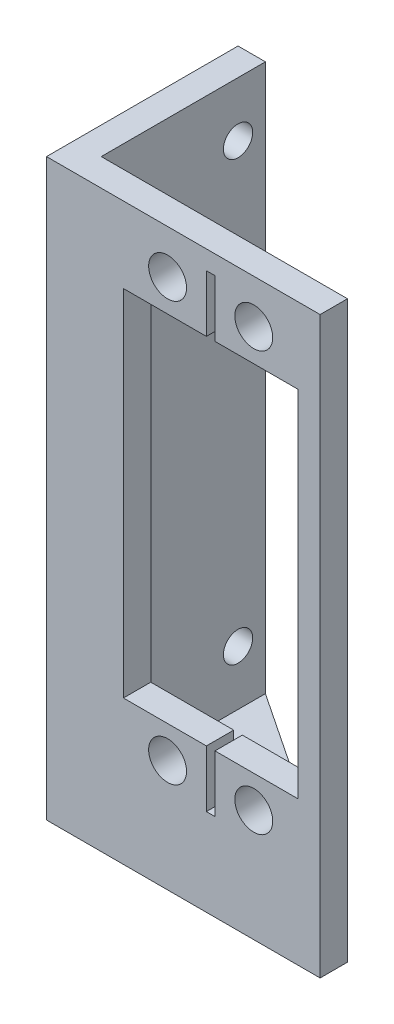
SolidWorks part; units mm, degrees
ref_plane "Front Plane" through (0, 0, 0) normal (0, 0, 1) x (1, 0, 0)
ref_plane "Top Plane" through (0, 0, 0) normal (0, 1, 0) x (1, 0, 0)
ref_plane "Right Plane" through (0, 0, 0) normal (1, 0, 0) x (0, 0, -1)
sketch "Sketch2" plane through (0, 0, 0) normal (0, 0, 1) x (1, 0, 0)
  line L1 (0, 0) -> (31.75, 0)
  line L2 (0, 0) -> (0, 63.5)
  line L3 (0, 63.5) -> (31.75, 63.5)
  line L4 (31.75, 0) -> (31.75, 63.5)
  dimension "D1" = 63.5
  dimension "D2" = 31.75
extrude "Boss-Extrude1" add sketch "Sketch2" along normal blind 3.175 contours L4 L3 L2 L1
sketch "Sketch3" plane through (0, 0, 3.175) normal (0, 0, 1) x (1, 0, 0)
  line L0 (8.923, 54.704) -> (29.177, 13.55) construction
  line L1 (8.923, 54.704) -> (18.55, 54.704)
  line L2 (8.923, 54.704) -> (8.923, 13.55)
  line L3 (8.923, 13.55) -> (18.55, 13.55)
  line L4 (29.177, 54.704) -> (29.177, 13.55)
  line L5 (29.177, 54.704) -> (8.923, 13.55) construction
  line L6 (14.05, 58.427) -> (24.05, 9.827) construction
  line L7 (14.05, 9.827) -> (24.05, 58.427) construction
  line L8 (19.55, 13.55) -> (29.177, 13.55)
  line L9 (18.55, 13.55) -> (18.55, 6.946)
  line L10 (18.55, 6.946) -> (19.55, 6.946)
  line L11 (19.55, 13.55) -> (19.55, 6.946)
  line L12 (19.05, 34.127) -> (62.1329, 34.127) construction
  line L13 (18.55, 61.308) -> (19.55, 61.308)
  line L14 (18.55, 54.704) -> (18.55, 61.308)
  line L15 (19.55, 54.704) -> (19.55, 61.308)
  line L16 (19.55, 54.704) -> (29.177, 54.704)
  line L17 (0, 0) -> (0, 63.5) construction
  line L18 (0, 63.5) -> (31.75, 63.5) construction
  circle A0 centre (14.05, 9.827) radius 2.2
  circle A1 centre (24.05, 9.827) radius 2.2
  circle A2 centre (14.05, 58.427) radius 2.2
  circle A3 centre (24.05, 58.427) radius 2.2
  point P8 (19.05, 6.946)
  point P17 (19.05, 34.127)
  point P18 (19.05, 34.127)
  point P27 (19.05, 44.45)
  dimension "D3" = 4.4
  dimension "D1" = 10
  dimension "D2" = 48.6
  dimension "D4" = 41.154
  dimension "D5" = 20.254
  dimension "D6" = 1
  dimension "D7" = 6.604
  dimension "D8" = 30.9
  dimension "D9" = 19.05
  dimension "D10" = 19.05
extrude "Cut-Extrude1" cut sketch "Sketch3" against normal through all
sketch "Sketch4" plane through (0, 0, 3.175) normal (0, 0, 1) x (1, 0, 0)
  line L0 (0, 0) -> (31.75, 0) construction
  line L1 (0, 63.5) -> (3.175, 63.5)
  line L2 (0, 63.5) -> (0, 0)
  line L3 (0, 0) -> (3.175, 0)
  line L4 (3.175, 63.5) -> (3.175, 0)
  dimension "D1" = 3.175
extrude "Boss-Extrude2" add sketch "Sketch4" against normal blind 19.05 from surface starting at face at (26.25, 9.827, 0)
sketch "Sketch5" plane through (0, 0, 0) normal (0, -1, 0) x (1, 0, 0)
  line L0 (0, 3.175) -> (31.75, 3.175)
  line L1 (31.75, 3.175) -> (31.75, 0)
  line L2 (31.75, 0) -> (3.175, -19.05)
  line L3 (3.175, -19.05) -> (0, -19.05)
  line L4 (0, -19.05) -> (0, 3.175)
extrude "Boss-Extrude3" add sketch "Sketch5" along normal blind 3.175
sketch "Sketch6" plane through (3.175, 0, 0) normal (1, 0, 0) x (0, 0, -1)
  line L0 (0, 0) -> (0, 63.5) construction
  line L1 (19.05, 0) -> (19.05, 63.5) construction
  line L2 (19.05, 63.5) -> (0, 63.5) construction
  line L4 (19.05, 0) -> (0, 0) construction
  circle A0 centre (3.175, 57.15) radius 1.7
  circle A1 centre (3.175, 6.35) radius 1.7
  circle A2 centre (15.875, 57.15) radius 1.7
  circle A3 centre (15.875, 6.35) radius 1.7
  dimension "D5" = 3.4
  dimension "D1" = 3.175
  dimension "D2" = 3.175
  dimension "D3" = 6.35
  dimension "D4" = 6.35
extrude "Cut-Extrude2" cut sketch "Sketch6" against normal through all
equation "\"D8@Sketch3\"=30.9mm"
equation "\"tightTol\"= 0.005in"
equation "\"normTol\"= 0.01in"
equation "\"looseTol\"= 0.02in"
equation "\"D5@Sketch6\"=3.4mm"
equation "\"D3@Sketch3\"=4.4mm"
